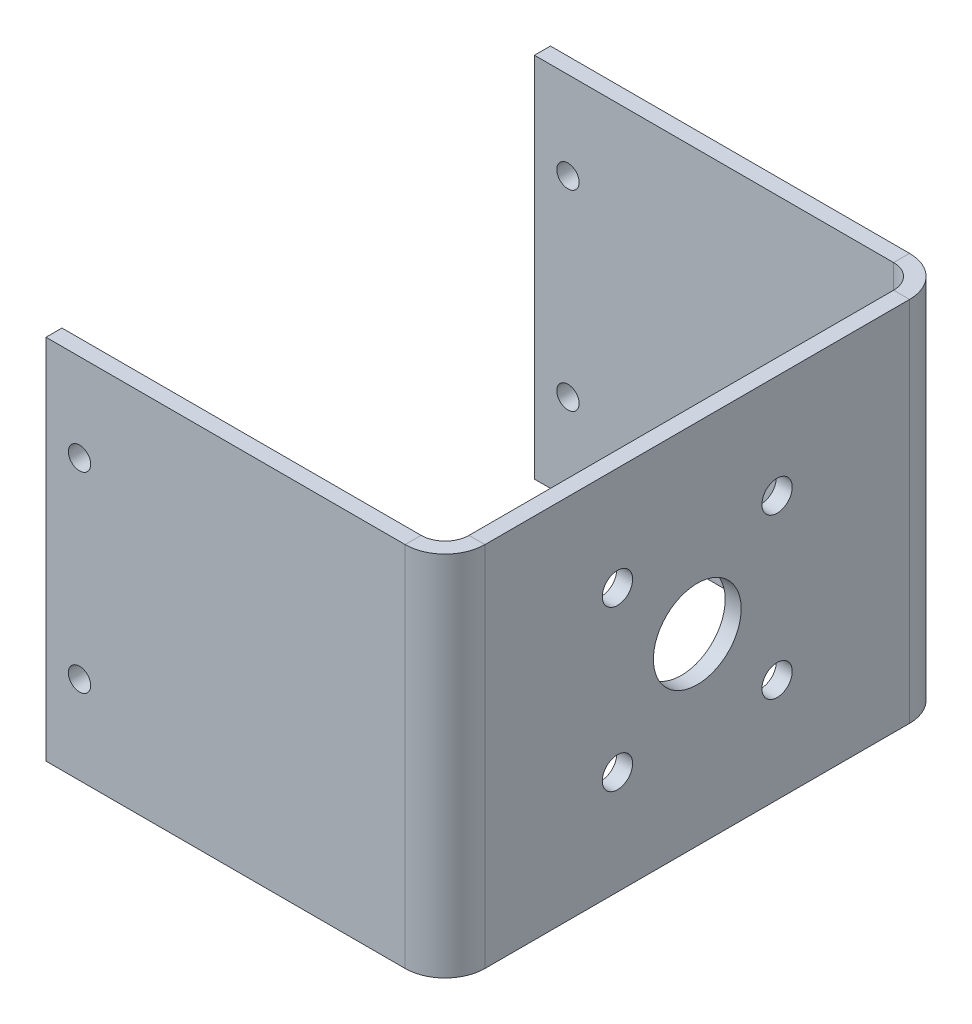
SolidWorks part; units mm, degrees
note: The reader was unsure of these and kept them because the rebuilt part matched: thickness of "Base-Flange1", "Edge-Flange1", "Sheet-Metal1", "Sheet-Metal2", "Sheet-Metal3", "Sheet-Metal5", "Sheet-Metal11", "Sheet-Metal12"; flange length of "Edge-Flange1".
material "Plain Carbon Steel"
ref_plane "Front Plane" through (0, 0, 0) normal (0, 0, 1) x (1, 0, 0)
ref_plane "Top Plane" through (0, 0, 0) normal (0, 1, 0) x (1, 0, 0)
ref_plane "Right Plane" through (0, 0, 0) normal (1, 0, 0) x (0, 0, -1)
sketch "Sketch1" plane through (0, 0, 0) normal (1, 0, 0) x (0, 0, -1)
  line L1 (-158, -115) -> (158, -115)
  line L2 (-158, -115) -> (-158, 115)
  line L3 (-158, 115) -> (158, 115)
  line L4 (158, -115) -> (158, 115)
  line L5 (-158, -115) -> (158, 115) construction
  line L6 (-158, 115) -> (158, -115) construction
  point P0 (0, 0)
  dimension "D1" = 316
  dimension "D2" = 230
base flange "Base-Flange1" sketch "Sketch1" thickness 10 reverse thickness direction no parameters "D1"=15
edge flange "Edge-Flange1" sketch "Sketch10" flange profiles "Sketch10", "Sketch11" flange angle 90 flange length 250 flange position material inside bend radius 15 thickness 10 relief rectangular parameters "D6"=10, "D8"=1
sketch "Sketch10" plane through (-10, 0, 158) normal (0, 0, 1) x (0, 1, 0)
  line L0 (115, 0) -> (-115, 0) construction
  line L1 (115, 0) -> (-115, 0)
  line L2 (-115, 0) -> (-115, 240)
  line L3 (-115, 240) -> (115, 240)
  line L4 (115, 240) -> (115, 0)
sketch "Sketch11" plane through (-10, 0, -158) normal (0, 0, -1) x (0, -1, 0)
  line L0 (115, 0) -> (-115, 0) construction
  line L1 (115, 0) -> (-115, 0)
  line L2 (-115, 0) -> (-115, 240)
  line L3 (-115, 240) -> (115, 240)
  line L4 (115, 240) -> (115, 0)
bend "EdgeBend1" bend radius 15 bend angle 90 parameters "D5"=1
bend "EdgeBend2" bend radius 15 bend angle 90 parameters "D5"=2
sketch "Sketch12" plane through (0, 0, 0) normal (1, 0, 0) x (0, 0, -1)
  line L0 (-158, -115) -> (158, 115) construction
  circle A0 centre (0, 0) radius 27.5
  dimension "D1" = 55
extrude "Cut-Extrude1" cut sketch "Sketch12" against normal blind 10
sketch "Sketch14" plane through (0, 0, 0) normal (1, 0, 0) x (0, 0, -1)
  line L1 (50, -50) -> (-50, -50) construction
  line L2 (50, -50) -> (50, 50) construction
  line L3 (50, 50) -> (-50, 50) construction
  line L4 (-50, -50) -> (-50, 50) construction
  line L5 (50, -50) -> (-50, 50) construction
  line L6 (50, 50) -> (-50, -50) construction
  circle A0 centre (-50, 50) radius 9.5
  circle A6 centre (0, 0) radius 70.7107 construction
  dimension "D1" = 19
  dimension "D2" = 100
extrude "Cut-Extrude3" cut sketch "Sketch14" against normal blind 10
pattern_circular "CirPattern1" count 4 over 360 about axis through (0, 0, 0) along (1, 0, 0) of "Cut-Extrude3" reverse direction yes
sketch "Sketch17" plane through (0, 0, 158) normal (0, 0, 1) x (1, 0, 0)
  circle A1 centre (-229, 60) radius 7
  circle A3 centre (-229, -60) radius 7
  dimension "D1" = 60
  dimension "D2" = 120
extrude "Cut-Extrude4" cut sketch "Sketch17" against normal through all
sketch "Bend-Lines1" [suppressed] plane through (0, 0, 0) normal (0, 1, 0) x (1, 0, 0)
sketch "Bounding-Box1" [suppressed] plane through (0, 0, 0) normal (0, 1, 0) x (1, 0, 0)
sheet metal parameters "Sheet-Metal1" thickness 10 parameters "D1"=15
flat pattern "Flat-Pattern1" [suppressed]
sketch "Bend-Lines2" plane through (0, 0, 0) normal (0, 1, 0) x (1, 0, 0)
sketch3d "Bounding-Box2" [suppressed]
  line L0 (-162, -100, 0) -> (162, -100, 0) construction
  line L1 (-162, 100, 0) -> (162, 100, 0) construction
  line L2 (-162, -100, 0) -> (-162, 100, 0) construction
  line L3 (162, -100, 0) -> (162, 100, 0) construction
sheet metal parameters "Sheet-Metal2" thickness 10 parameters "D1"=15
flat pattern "Flat-Pattern1"
sketch "Bend-Lines2" plane through (0, 0, 0) normal (1, 0, 0) x (0, 0, -1)
  line L0 (152.708, -100) -> (152.708, 100) construction
  line L1 (-152.708, 100) -> (-152.708, -100) construction
  line L2 (152.708, -100) -> (152.708, 100) construction
  line L3 (-152.708, 100) -> (-152.708, -100) construction
sketch3d "Bounding-Box2" [suppressed]
  line L0 (416.4159, -100, 0) -> (-416.4159, -100, 0) construction
  line L1 (416.4159, 100, 0) -> (-416.4159, 100, 0) construction
  line L2 (416.4159, -100, 0) -> (416.4159, 100, 0) construction
  line L3 (-416.4159, -100, 0) -> (-416.4159, 100, 0) construction
bend of the flat pattern "Flatten-<EdgeBend1>1"
bend of the flat pattern "Flatten-<EdgeBend2>1"
sheet metal parameters "Sheet-Metal3" thickness 10 parameters "D1"=15
flat pattern "Flat-Pattern1"
sketch "Bend-Lines2" plane through (0, 0, 0) normal (1, 0, 0) x (0, 0, -1)
  line L0 (152.708, -100) -> (152.708, 100) construction
  line L1 (-152.708, 100) -> (-152.708, -100) construction
  line L2 (152.708, -100) -> (152.708, 100) construction
  line L3 (-152.708, 100) -> (-152.708, -100) construction
sketch3d "Bounding-Box2" [suppressed]
  line L0 (416.4159, -100, 0) -> (-416.4159, -100, 0) construction
  line L1 (416.4159, 100, 0) -> (-416.4159, 100, 0) construction
  line L2 (416.4159, -100, 0) -> (416.4159, 100, 0) construction
  line L3 (-416.4159, -100, 0) -> (-416.4159, 100, 0) construction
bend of the flat pattern "Flatten-<EdgeBend1>1"
bend of the flat pattern "Flatten-<EdgeBend2>1"
sheet metal parameters "Sheet-Metal5" thickness 10 parameters "D1"=15
flat pattern "Flat-Pattern1"
sketch "Bend-Lines2" plane through (0, 0, 0) normal (1, 0, 0) x (0, 0, -1)
  line L0 (152.708, -100) -> (152.708, 100) construction
  line L1 (-152.708, 100) -> (-152.708, -100) construction
  line L2 (152.708, -100) -> (152.708, 100) construction
  line L3 (-152.708, 100) -> (-152.708, -100) construction
sketch3d "Bounding-Box2" [suppressed]
  line L0 (416.4159, -100, 0) -> (-416.4159, -100, 0) construction
  line L1 (416.4159, 100, 0) -> (-416.4159, 100, 0) construction
  line L2 (416.4159, -100, 0) -> (416.4159, 100, 0) construction
  line L3 (-416.4159, -100, 0) -> (-416.4159, 100, 0) construction
bend of the flat pattern "Flatten-<EdgeBend1>1"
bend of the flat pattern "Flatten-<EdgeBend2>1"
sheet metal parameters "Sheet-Metal11" thickness 10 parameters "D1"=15
flat pattern "Flat-Pattern1" [suppressed]
sketch "Bend-Lines2" plane through (0, 0, 0) normal (1, 0, 0) x (0, 0, -1)
  line L0 (148.708, -115) -> (148.708, 115) construction
  line L1 (-148.708, 115) -> (-148.708, -115) construction
  line L2 (148.708, -115) -> (148.708, 115) construction
  line L3 (-148.708, 115) -> (-148.708, -115) construction
sketch3d "Bounding-Box2" [suppressed]
  line L0 (389.4159, -115, 0) -> (-389.4159, -115, 0) construction
  line L1 (389.4159, 115, 0) -> (-389.4159, 115, 0) construction
  line L2 (389.4159, -115, 0) -> (389.4159, 115, 0) construction
  line L3 (-389.4159, -115, 0) -> (-389.4159, 115, 0) construction
bend of the flat pattern "Flatten-<EdgeBend1>1"
bend of the flat pattern "Flatten-<EdgeBend2>1"
sketch "Sketch13-1" [suppressed] plane through (0, 0, 139.4159) normal (1, 0, 0) x (0, 0, -1)
  line L1 (-250, 115) -> (-250, -115) construction
  circle A0 centre (-229, 60) radius 7.5
  dimension "D1" = 15
  dimension "D2" = 60
  dimension "D3" = 21
sheet metal parameters "Sheet-Metal12" thickness 10 parameters "D1"=15
flat pattern "Flat-Pattern1"
sketch "Bend-Lines2" plane through (0, 0, 0) normal (1, 0, 0) x (0, 0, -1)
  line L0 (148.708, -115) -> (148.708, 115) construction
  line L1 (-148.708, 115) -> (-148.708, -115) construction
  line L2 (148.708, -115) -> (148.708, 115) construction
  line L3 (-148.708, 115) -> (-148.708, -115) construction
sketch3d "Bounding-Box2" [suppressed]
  line L0 (389.4159, -115, 0) -> (-389.4159, -115, 0) construction
  line L1 (389.4159, 115, 0) -> (-389.4159, 115, 0) construction
  line L2 (389.4159, -115, 0) -> (389.4159, 115, 0) construction
  line L3 (-389.4159, -115, 0) -> (-389.4159, 115, 0) construction
bend of the flat pattern "Flatten-<EdgeBend1>1"
bend of the flat pattern "Flatten-<EdgeBend2>1"
